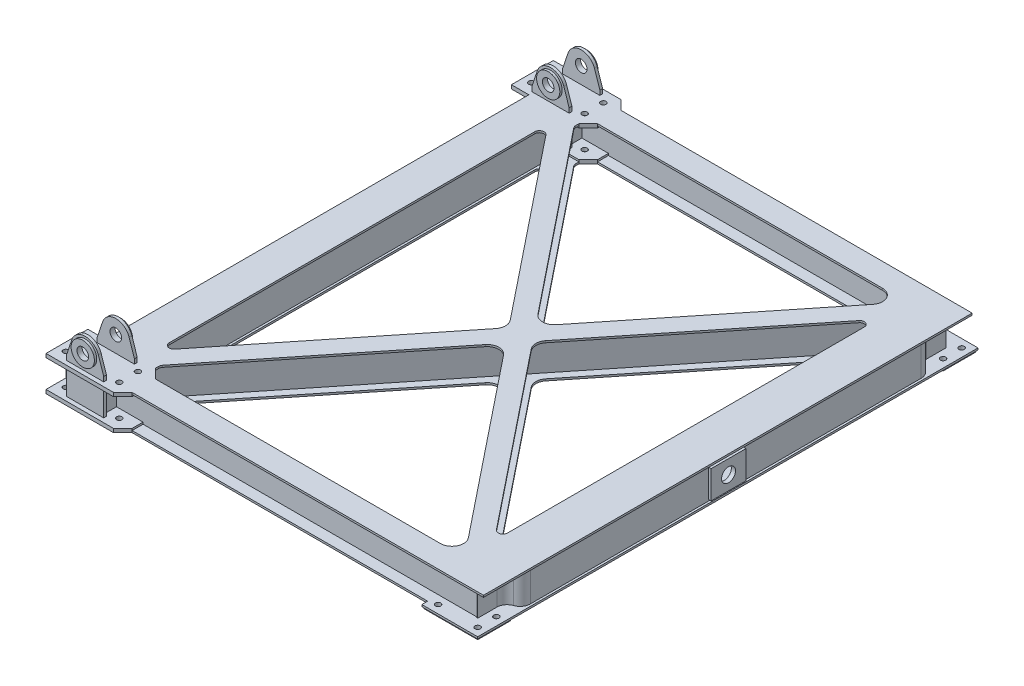
SolidWorks part; units mm, degrees
ref_plane "前视基准面" through (0, 0, 0) normal (0, 0, 1) x (1, 0, 0)
ref_plane "上视基准面" through (0, 0, 0) normal (0, 1, 0) x (1, 0, 0)
ref_plane "右视基准面" through (0, 0, 0) normal (1, 0, 0) x (0, 0, -1)
sketch "草图1" plane through (0, 0, 0) normal (0, 1, 0) x (1, 0, 0)
  line L1 (0, 0) -> (1765, 0)
  line L2 (0, 0) -> (0, 2150)
  line L3 (0, 2150) -> (1765, 2150)
  line L4 (1765, 0) -> (1765, 2150)
  dimension "D1" = 1765
  dimension "D2" = 2150
extrude "凸台-拉伸1" add sketch "草图1" along normal blind 8
sketch "草图2" plane through (0, 8, 0) normal (0, 1, 0) x (1, 0, 0)
  line L0 (1675, 544.2573) -> (1675, 50544.2573) construction
  line L1 (75, 259.5394) -> (75, 50259.5394) construction
  line L2 (367.575, 2075) -> (50367.575, 2075) construction
  line L3 (283.2141, 75) -> (50283.2141, 75) construction
  line L4 (1765, 0) -> (1765, 2150) construction
  line L7 (0, 2150) -> (0, 0) construction
  line L8 (-1000, 1075) -> (49000, 1075) construction
  line L9 (75, 2075) -> (1675, 75) construction
  line L10 (1675, 2075) -> (75, 75) construction
  line L11 (215, 2025) -> (1583.775, 2025)
  line L12 (1583.775, 2025) -> (875, 1139.0312)
  line L13 (215, 2025) -> (215, 1964.0312)
  line L14 (1585, 251.5312) -> (926.225, 1075)
  line L15 (926.225, 1075) -> (1585, 1898.4688)
  line L16 (1585, 1898.4688) -> (1585, 251.5312)
  line L17 (150, 1917.2188) -> (823.775, 1075)
  line L18 (823.775, 1075) -> (150, 232.7812)
  line L19 (150, 232.7812) -> (150, 1917.2188)
  line L20 (215, 1964.0312) -> (875, 1139.0312)
  line L21 (875, 1010.9688) -> (1583.775, 125)
  line L22 (1583.775, 125) -> (215, 125)
  line L23 (215, 125) -> (215, 185.9688)
  line L24 (0, 2150) -> (1525, 2150)
  line L25 (0, 2150) -> (0, 2125)
  line L26 (0, 2125) -> (1525, 2125)
  line L27 (1525, 2150) -> (1525, 2125)
  line L28 (0, 0) -> (1525, 0)
  line L29 (0, 0) -> (0, 25)
  line L30 (0, 25) -> (1525, 25)
  line L31 (1525, 0) -> (1525, 25)
  line L32 (215, 185.9688) -> (875, 1010.9688)
  point P15 (0, 1075)
  dimension "D1" = 90
  dimension "D2" = 75
  dimension "D3" = 1000
  dimension "D4" = 1000
  dimension "D5" = 90
  dimension "D6" = 40
  dimension "D7" = 40
  dimension "D8" = 40
  dimension "D9" = 40
  dimension "D10" = 75
  dimension "D11" = 50
  dimension "D12" = 50
  dimension "D13" = 240
  dimension "D14" = 50
  dimension "D15" = 240
  dimension "D16" = 50
  dimension "D17" = 215
  dimension "D18" = 215
extrude "切除-拉伸1" cut sketch "草图2" against normal through all
sketch "草图4" plane through (0, 8, 0) normal (0, 1, 0) x (1, 0, 0)
  line L0 (1525, 2125) -> (1525, 2150) construction
  line L1 (0, 25) -> (255, 25)
  line L2 (0, 25) -> (0, 165)
  line L3 (0, 165) -> (255, 165)
  line L4 (255, 25) -> (255, 165)
  line L5 (0, 2125) -> (255, 2125)
  line L6 (0, 2125) -> (0, 1985)
  line L7 (0, 1985) -> (255, 1985)
  line L8 (255, 2125) -> (255, 1985)
  line L9 (1525, 0) -> (1525, 25) construction
  line L10 (765, 1075) -> (50765, 1075) construction
  line L11 (1765, 0) -> (1765, 2150) construction
  point P10 (1525, 2137.5)
  point P20 (1765, 1075)
  dimension "D1" = 1270
  dimension "D2" = 1270
  dimension "D3" = 910
  dimension "D4" = 910
extrude "切除-拉伸2" cut sketch "草图4" against normal through all
sketch "草图6" plane through (0, 8, 0) normal (0, 1, 0) x (1, 0, 0)
  line L0 (1765, 1075) -> (0, 1075) construction
  line L1 (150, 1917.2188) -> (150, 232.7812) construction
  line L2 (135, 2072) -> (141, 2072)
  line L3 (1765, 0) -> (1765, 2150) construction
  line L4 (0, 1985) -> (0, 165) construction
  line L5 (882.5, 75) -> (882.5, 50075) construction
  line L6 (75, 252.5093) -> (75, 50252.5093) construction
  line L7 (15, 2081) -> (9, 2081)
  line L8 (15, 2081) -> (15, 69)
  line L9 (15, 69) -> (9, 69)
  line L10 (9, 2081) -> (9, 69)
  line L11 (1675, 136.5131) -> (1675, 50136.5131) construction
  line L12 (135, 2072) -> (135, 78)
  line L14 (1750, 1915) -> (1750, 235)
  line L15 (1690, 2081) -> (1690, 1998.4266)
  line L16 (1756, 1915) -> (1756, 235)
  line L17 (1600, 2072) -> (1594, 2072)
  line L18 (1600, 2072) -> (1600, 78)
  line L19 (1600, 78) -> (1594, 78)
  line L20 (1594, 2072) -> (1594, 78)
  line L21 (135, 78) -> (141, 78)
  line L22 (141, 2072) -> (141, 78)
  line L23 (1690, 151.5734) -> (1690, 69)
  line L24 (1690, 69) -> (1696, 69)
  line L25 (1696, 69) -> (1696, 151.5734)
  line L26 (1690, 2081) -> (1696, 2081)
  line L27 (1696, 2081) -> (1696, 1998.4266)
  arc A0 (1750, 235) -> (1720, 193.2867) centre (1706, 235) cw
  arc A1 (1720, 193.2867) -> (1690, 151.5734) centre (1734, 151.5734) ccw
  arc A2 (1756, 235) -> (1726, 193.2867) centre (1712, 235) cw
  arc A3 (1726, 193.2867) -> (1696, 151.5734) centre (1740, 151.5734) ccw
  arc A4 (1690, 1998.4266) -> (1720, 1956.7133) centre (1734, 1998.4266) ccw
  arc A5 (1720, 1956.7133) -> (1750, 1915) centre (1706, 1915) cw
  arc A6 (1696, 1998.4266) -> (1726, 1956.7133) centre (1740, 1998.4266) ccw
  arc A7 (1726, 1956.7133) -> (1756, 1915) centre (1712, 1915) cw
  point P10 (882.5, 1075)
  dimension "D14" = 44
  dimension "D15" = 44
  dimension "D16" = 44
  dimension "D17" = 44
  dimension "D21" = 44
  dimension "D22" = 44
  dimension "D23" = 44
  dimension "D24" = 44
  dimension "D1" = 1006
  dimension "D2" = 1006
  dimension "D3" = 6
  dimension "D4" = 75
  dimension "D5" = 90
  dimension "D6" = 60
  dimension "D7" = 75
  dimension "D8" = 997
  dimension "D9" = 997
  dimension "D10" = 6
  dimension "D11" = 75
  dimension "D12" = 60
  dimension "D13" = 15
  dimension "D18" = 840
  dimension "D19" = 15
  dimension "D20" = 840
  dimension "D25" = 6
extrude "凸台-拉伸3" add sketch "草图6" along normal blind 134
sketch "草图7" plane through (0, 8, 0) normal (0, 1, 0) x (1, 0, 0)
  line L0 (1750, 1075) -> (15, 1075) construction
  line L1 (1750, 1915) -> (1750, 235) construction
  line L2 (15, 69) -> (15, 2081) construction
  line L3 (882.5, 75) -> (882.5, 50075) construction
  line L4 (549.0462, 2075) -> (50549.0462, 2075) construction
  line L5 (-117.5, 75) -> (49882.5, 75) construction
  line L6 (882.5, 1075) -> (32117.2524, 40118.4405) construction
  line L7 (70.5, 2078) -> (1694.5, 2078)
  line L8 (70.5, 2078) -> (70.5, 2072)
  line L9 (70.5, 2072) -> (1694.5, 2072)
  line L10 (1694.5, 2078) -> (1694.5, 2072)
  line L11 (70.5, 78) -> (1694.5, 78)
  line L12 (70.5, 78) -> (70.5, 72)
  line L13 (70.5, 72) -> (1694.5, 72)
  line L14 (1694.5, 78) -> (1694.5, 72)
  line L15 (882.5, 1075) -> (32117.2524, 40118.4405) construction
  line L16 (1585, 1898.4688) -> (926.225, 1075) construction
  line L17 (882.5, 1075) -> (-30352.2524, 40118.4405) construction
  line L18 (215, 1964.0312) -> (875, 1139.0312) construction
  line L19 (1594, 1969.1773) -> (1594, 1959.5727)
  line L20 (1594, 2072) -> (1594, 78) construction
  line L21 (1594, 1959.5727) -> (886.3419, 1075)
  line L22 (886.3419, 1075) -> (1594, 190.4273)
  line L23 (1594, 190.4273) -> (1594, 180.8227)
  line L24 (1594, 180.8227) -> (882.5, 1070.1977)
  line L25 (882.5, 1070.1977) -> (141, 143.3227)
  line L26 (141, 78) -> (141, 2072) construction
  line L27 (141, 143.3227) -> (141, 152.9273)
  line L28 (141, 152.9273) -> (878.6581, 1075)
  line L29 (878.6581, 1075) -> (141, 1997.0727)
  line L30 (141, 1997.0727) -> (141, 2006.6773)
  line L31 (141, 2006.6773) -> (882.5, 1079.8023)
  line L32 (882.5, 1079.8023) -> (1594, 1969.1773)
  point P10 (882.5, 1075)
  dimension "D1" = 1000
  dimension "D2" = 1000
  dimension "D3" = 812
  dimension "D4" = 812
  dimension "D5" = 3
  dimension "D6" = 3
  dimension "D7" = 812
  dimension "D8" = 812
  dimension "D9" = 3
  dimension "D10" = 3
  dimension "D11" = 3
  dimension "D12" = 3
  dimension "D13" = 3
  dimension "D14" = 3
extrude "凸台-拉伸5" add sketch "草图7" along normal blind 134
sketch "草图10" plane through (0, 142, 0) normal (0, 1, 0) x (1, 0, 0)
  line L0 (1765, 1075) -> (0, 1075) construction
  line L1 (0, 2125) -> (1765, 2125)
  line L2 (0, 2125) -> (0, 25)
  line L3 (0, 25) -> (1765, 25)
  line L4 (1765, 2125) -> (1765, 25)
  line L5 (1765, 0) -> (1765, 2150) construction
  line L6 (0, 1985) -> (0, 165) construction
  line L7 (882.5, 75) -> (882.5, 50075) construction
  line L8 (255, 2125) -> (1525, 2125) construction
  line L9 (1525, 25) -> (255, 25) construction
  point P14 (882.5, 1075)
extrude "凸台-拉伸6" add sketch "草图10" along normal blind 8
sketch "草图11" plane through (0, 150, 0) normal (0, 1, 0) x (1, 0, 0)
  line L0 (0, 2125) -> (255, 2125)
  line L1 (1765, 25) -> (1765, 2125) construction
  line L2 (255, 2125) -> (255, 2025)
  line L3 (0, 25) -> (1765, 25) construction
  line L4 (1675, 171.6635) -> (1675, 50171.6635) construction
  line L5 (75, 361.4754) -> (75, 50361.4754) construction
  line L6 (0, 2125) -> (0, 25) construction
  line L7 (-799.417, 2075) -> (49200.583, 2075) construction
  line L8 (-732.6313, 75) -> (49267.3687, 75) construction
  line L9 (1765, 2125) -> (0, 2125) construction
  line L10 (1675, 2075) -> (75, 75) construction
  line L11 (75, 2075) -> (1675, 75) construction
  line L12 (255, 2025) -> (1583.775, 2025)
  line L13 (1583.775, 2025) -> (875, 1139.0312)
  line L14 (875, 1139.0312) -> (215, 1964.0312)
  line L15 (215, 1964.0312) -> (215, 1985)
  line L16 (0, 1985) -> (0, 2125)
  line L17 (823.775, 1075) -> (150, 232.7812)
  line L18 (150, 232.7812) -> (150, 1917.2188)
  line L19 (150, 1917.2188) -> (823.775, 1075)
  line L20 (1585, 1898.4688) -> (926.225, 1075)
  line L21 (926.225, 1075) -> (1585, 251.5312)
  line L22 (1585, 251.5312) -> (1585, 1898.4688)
  line L23 (0, 25) -> (0, 165)
  line L24 (0, 165) -> (215, 165)
  line L25 (215, 165) -> (215, 185.9688)
  line L26 (215, 185.9688) -> (875, 1010.9688)
  line L27 (875, 1010.9688) -> (1583.775, 125)
  line L28 (1583.775, 125) -> (255, 125)
  line L29 (255, 125) -> (255, 25)
  line L30 (255, 25) -> (0, 25)
  line L31 (0, 1985) -> (215, 1985)
  line L32 (1525, 0) -> (1525, 25) construction
  line L33 (1525, 2125) -> (1525, 2150) construction
  dimension "D1" = 90
  dimension "D2" = 75
  dimension "D3" = 50
  dimension "D4" = 50
  dimension "D5" = 40
  dimension "D6" = 40
  dimension "D7" = 40
  dimension "D8" = 40
  dimension "D9" = 90
  dimension "D10" = 75
  dimension "D11" = 50
  dimension "D12" = 50
  dimension "D13" = 215
  dimension "D14" = 215
  dimension "D15" = 90
  dimension "D16" = 90
  dimension "D17" = 1270
  dimension "D18" = 1270
extrude "切除-拉伸3" cut sketch "草图11" against normal blind 8
fillet "圆角3" radius 50 12 edges at (926.225, 4, -1075) (926.225, 146, -1075) (875, 4, -1139.0312) (875, 146, -1139.0312) (823.775, 4, -1075) (823.775, 146, -1075) (875, 146, -1010.9688) (875, 4, -1010.9688) (1583.775, 146, -2025) (1583.775, 4, -2025) (1583.775, 146, -125) (1583.775, 4, -125)
fillet "圆角4" radius 20 12 edges at (150, 146, -1917.2188) (150, 4, -1917.2188) (1585, 146, -1898.4688) (1585, 4, -1898.4688) (1585, 146, -251.5312) (1585, 4, -251.5312) (150, 4, -232.7812) (150, 146, -232.7812) (215, 146, -1964.0312) (215, 4, -1964.0312) (215, 4, -185.9688) (215, 146, -185.9688)
sketch "草图13" plane through (0, 0, 0) normal (0, -1, 0) x (1, 0, 0)
  line L0 (255, -125) -> (255, -25)
  line L1 (255, -25) -> (215, 15)
  line L2 (215, 15) -> (-75, 15)
  line L3 (-75, 15) -> (-75, -165)
  line L4 (-75, -165) -> (215, -165)
  line L5 (215, -165) -> (255, -125)
  line L6 (255, -2025) -> (215, -1985)
  line L7 (215, -1985) -> (-75, -1985)
  line L8 (-75, -1985) -> (-75, -2165)
  line L9 (-75, -2165) -> (215, -2165)
  line L10 (215, -2165) -> (255, -2125)
  line L11 (255, -2125) -> (255, -2025)
  line L12 (-745, -75) -> (49255, -75) construction
  line L13 (-745, -2075) -> (49255, -2075) construction
  line L14 (-40, -1091.8576) -> (-40, 48908.1424) construction
  line L15 (190, -1108.9004) -> (190, 48891.0996) construction
  line L16 (-1094.3487, -35) -> (48905.6513, -35) construction
  line L17 (-1100.2766, -115) -> (48899.7234, -115) construction
  line L18 (-1140.3694, -2035) -> (48859.6306, -2035) construction
  line L19 (-1147.3703, -2115) -> (48852.6297, -2115) construction
  circle A0 centre (-40, -2035) radius 11.5
  circle A1 centre (-40, -2115) radius 11.5
  circle A2 centre (190, -2035) radius 11.5
  circle A3 centre (190, -2115) radius 11.5
  circle A4 centre (190, -35) radius 11.5
  circle A5 centre (190, -115) radius 11.5
  circle A6 centre (-40, -35) radius 11.5
  circle A7 centre (-40, -115) radius 11.5
  point P19 (255, -75)
  point P22 (255, -2075)
  dimension "D13" = 23
  dimension "D14" = 23
  dimension "D1" = 290
  dimension "D2" = 180
  dimension "D3" = 330
  dimension "D4" = 180
  dimension "D5" = 290
  dimension "D6" = 330
  dimension "D7" = 35
  dimension "D8" = 230
  dimension "D9" = 40
  dimension "D10" = 40
  dimension "D11" = 40
  dimension "D12" = 40
extrude "凸台-拉伸8" add sketch "草图13" against normal blind 16 separate body
pattern_linear "阵列(线性)1" count 2 spacing 134 along (0, 1, 0) of "凸台-拉伸8"
sketch "草图14" plane through (0, 150, 0) normal (0, 1, 0) x (1, 0, 0)
  line L0 (-1075, 2075) -> (48925, 2075) construction
  line L1 (-75, 1985) -> (-75, 2165) construction
  line L2 (-1075, 75) -> (48925, 75) construction
  line L3 (-75, -15) -> (-75, 165) construction
  line L4 (75, 228.6961) -> (75, 50228.6961) construction
  line L5 (0, 1985) -> (0, 165) construction
  line L7 (-5, 2147) -> (155, 2147)
  line L8 (-5, 2147) -> (-5, 2135)
  line L9 (-5, 2135) -> (155, 2135)
  line L10 (155, 2147) -> (155, 2135)
  line L11 (-5, 2015) -> (155, 2015)
  line L12 (-5, 2015) -> (-5, 2003)
  line L13 (-5, 2003) -> (155, 2003)
  line L14 (155, 2015) -> (155, 2003)
  line L15 (-5, 147) -> (155, 147)
  line L16 (-5, 147) -> (-5, 135)
  line L17 (-5, 135) -> (155, 135)
  line L18 (155, 147) -> (155, 135)
  line L19 (-5, 15) -> (155, 15)
  line L20 (-5, 15) -> (-5, 3)
  line L21 (-5, 3) -> (155, 3)
  line L22 (155, 15) -> (155, 3)
  point P5 (-75, 2075)
  point P10 (-75, 75)
  dimension "D1" = 75
  dimension "D2" = 80
  dimension "D3" = 80
  dimension "D4" = 12
  dimension "D5" = 60
  dimension "D6" = 60
  dimension "D7" = 60
  dimension "D8" = 60
extrude "凸台-拉伸9" add sketch "草图14" along normal blind 150
sketch "草图15" plane through (0, 0, -3) normal (0, 0, 1) x (1, 0, 0)
  line L0 (-5, 170) -> (-5, 300)
  line L1 (-5, 300) -> (-5, 150) construction
  line L2 (-5, 300) -> (155, 300)
  line L3 (155, 300) -> (155, 170)
  line L4 (155, 300) -> (155, 150) construction
  line L5 (18.1008, 239.0388) -> (-5, 170)
  line L6 (131.8992, 239.0388) -> (155, 170)
  line L7 (-5, 150) -> (155, 150) construction
  line L8 (215, 150) -> (-75, 150) construction
  arc A0 (131.8992, 239.0388) -> (18.1008, 239.0388) centre (75, 220) ccw
  circle A1 centre (75, 220) radius 25
  dimension "D4" = 60
  dimension "D5" = 50
  dimension "D1" = 80
  dimension "D2" = 20
  dimension "D3" = 70
extrude "切除-拉伸4" cut sketch "草图15" against normal through all
sketch "草图16" plane through (0, 150, 0) normal (0, 1, 0) x (1, 0, 0)
  line L1 (-5, 15) -> (155, 15)
  line L2 (-5, 15) -> (-5, 3)
  line L3 (-5, 3) -> (155, 3)
  line L4 (155, 15) -> (155, 3)
  line L5 (-5, 147) -> (155, 147)
  line L6 (-5, 147) -> (-5, 135)
  line L7 (-5, 135) -> (155, 135)
  line L8 (155, 147) -> (155, 135)
  line L9 (-5, 2015) -> (155, 2015)
  line L10 (-5, 2015) -> (-5, 2003)
  line L11 (-5, 2003) -> (155, 2003)
  line L12 (155, 2015) -> (155, 2003)
  line L13 (-5, 2147) -> (155, 2147)
  line L14 (-5, 2147) -> (-5, 2135)
  line L15 (-5, 2135) -> (155, 2135)
  line L16 (155, 2147) -> (155, 2135)
extrude "凸台-拉伸10" add sketch "草图16" against normal blind 134
sketch "草图17" plane through (-75, 0, 0) normal (-1, 0, 0) x (0, 0, 1)
  line L0 (-75, -850) -> (-75, 49150) construction
  line L1 (15, 150) -> (-165, 150) construction
  line L2 (-69, 134) -> (-135, 134) construction
  line L3 (-78, 134) -> (-72, 134)
  line L4 (-78, 134) -> (-78, 16)
  line L5 (-78, 16) -> (-72, 16)
  line L6 (-72, 134) -> (-72, 16)
  line L7 (15, 16) -> (-165, 16) construction
  line L8 (-2075, -1000) -> (-2075, 49000) construction
  line L9 (-1985, 0) -> (-2165, 0) construction
  line L10 (-1985, 134) -> (-2165, 134) construction
  line L11 (-2078, 134) -> (-2072, 134)
  line L12 (-2078, 134) -> (-2078, 16)
  line L13 (-2078, 16) -> (-2072, 16)
  line L14 (-2072, 134) -> (-2072, 16)
  line L15 (-2015, 16) -> (-2081, 16) construction
  point P5 (-75, 150)
  point P18 (-2075, 0)
  dimension "D1" = 3
  dimension "D2" = 3
  dimension "D3" = 3
  dimension "D4" = 3
extrude "凸台-拉伸11" add sketch "草图17" against normal blind 84 separate body
sketch "草图18" plane through (0, 0, -3) normal (0, 0, 1) x (1, 0, 0)
  line L0 (75, -780) -> (75, 49220) construction
  line L1 (215, 134) -> (-75, 134) construction
  line L2 (9, 134) -> (15, 134)
  line L3 (9, 134) -> (9, 16)
  line L4 (9, 16) -> (15, 16)
  line L5 (15, 134) -> (15, 16)
  line L6 (-5, 16) -> (155, 16) construction
  line L7 (-5, 134) -> (155, 134) construction
  line L8 (135, 134) -> (141, 134)
  line L9 (135, 134) -> (135, 16)
  line L10 (135, 16) -> (141, 16)
  line L11 (141, 134) -> (141, 16)
  line L12 (215, 16) -> (-75, 16) construction
  dimension "D1" = 60
  dimension "D2" = 60
  dimension "D3" = 66
  dimension "D4" = 66
extrude "凸台-拉伸12" add sketch "草图18" against normal blind 2132
sketch "草图19" plane through (0, 0, -3) normal (0, 0, 1) x (1, 0, 0)
  circle A0 centre (75, 220) radius 50
  circle A1 centre (75, 220) radius 25
  circle A2 centre (75, 220) radius 25 construction
  dimension "D1" = 100
extrude "凸台-拉伸13" add sketch "草图19" along normal blind 10
pattern_linear "阵列(线性)2" count 2 spacing 154 along (0, 0, -1) of "凸台-拉伸13"
pattern_linear "阵列(线性)3" count 2 spacing 2000 along (0, 0, -1) of "凸台-拉伸13", "阵列(线性)2"
sketch "草图20" plane through (0, 0, 0) normal (0, -1, 0) x (1, 0, 0)
  line L0 (765, -1075) -> (50765, -1075) construction
  line L1 (1765, 0) -> (1765, -2150) construction
  line L2 (1675, -1882.4903) -> (1675, 48117.5097) construction
  line L3 (553.174, -75) -> (50553.174, -75) construction
  line L4 (788.8658, -2075) -> (50788.8658, -2075) construction
  line L6 (1530, -5) -> (1760, -5)
  line L7 (1530, -5) -> (1530, -145)
  line L8 (1530, -145) -> (1760, -145)
  line L9 (1760, -5) -> (1760, -145)
  line L10 (1530, -2005) -> (1760, -2005)
  line L11 (1530, -2005) -> (1530, -2145)
  line L12 (1530, -2145) -> (1760, -2145)
  line L13 (1760, -2005) -> (1760, -2145)
  point P5 (1765, -1075)
  dimension "D1" = 90
  dimension "D2" = 1000
  dimension "D3" = 1000
  dimension "D4" = 145
  dimension "D5" = 230
  dimension "D6" = 70
  dimension "D7" = 70
  dimension "D8" = 230
  dimension "D9" = 70
  dimension "D10" = 70
  dimension "D11" = 145
extrude "凸台-拉伸14" add sketch "草图20" along normal blind 8
sketch "草图21" plane through (0, -8, 0) normal (0, -1, 0) x (1, 0, 0)
  line L0 (1760, -75) -> (1530, -75) construction
  line L1 (1760, -145) -> (1760, -5) construction
  line L2 (1530, -5) -> (1530, -145) construction
  line L3 (1645, -5) -> (1645, -145) construction
  line L4 (1760, -5) -> (1530, -5) construction
  line L5 (1530, -145) -> (1760, -145) construction
  circle A0 centre (1560, -35) radius 11.5
  dimension "D1" = 23
  dimension "D2" = 85
  dimension "D3" = 40
extrude "切除-拉伸5" cut sketch "草图21" against normal blind 16
pattern_linear "阵列(线性)4" count 2 spacing 170 along (1, 0, 0) count 2 spacing 80 along (0, 0, -1) of "切除-拉伸5"
pattern_linear "阵列(线性)5" count 2 spacing 2000 along (0, 0, -1) of "切除-拉伸5", "阵列(线性)4"
sketch "草图23" plane through (1756, 0, 0) normal (1, 0, 0) x (0, 0, -1)
  line L0 (1075, -858) -> (1075, 49142) construction
  line L1 (235, 142) -> (1915, 142) construction
  line L2 (-765, 75) -> (49235, 75) construction
  line L3 (235, 142) -> (235, 8) construction
  line L5 (1000, 135) -> (1150, 135)
  line L6 (1000, 135) -> (1000, 15)
  line L7 (1000, 15) -> (1150, 15)
  line L8 (1150, 135) -> (1150, 15)
  point P5 (1075, 142)
  point P10 (235, 75)
  dimension "D1" = 150
  dimension "D2" = 120
  dimension "D3" = 60
  dimension "D4" = 75
extrude "凸台-拉伸15" add sketch "草图23" along normal blind 12
sketch "草图24" plane through (1768, 0, 0) normal (1, 0, 0) x (0, 0, -1)
  line L0 (1000, 135) -> (1000, 15) construction
  line L1 (1000, 15) -> (1150, 15) construction
  circle A0 centre (1075, 75) radius 30
  dimension "D1" = 60
  dimension "D2" = 75
  dimension "D3" = 60
extrude "切除-拉伸6" cut sketch "草图24" against normal blind 18
ref_plane "基准面2" through (1675, 0, 0) normal (1, 0, 0) x (0, 0, -1)
mirror "镜向1" about plane through (1675, 0, 0) normal (1, 0, 0) of "切除-拉伸6", "凸台-拉伸15"
